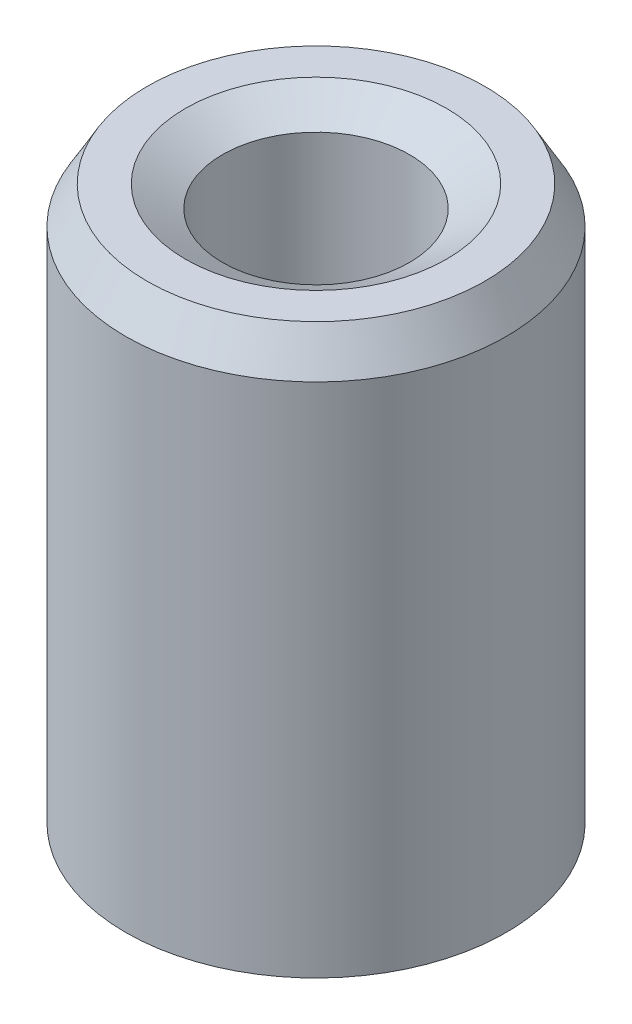
SolidWorks part; units mm, degrees
ref_plane "Front Plane" through (0, 0, 0) normal (0, 0, 1) x (1, 0, 0)
ref_plane "Top Plane" through (0, 0, 0) normal (0, 1, 0) x (1, 0, 0)
ref_plane "Right Plane" through (0, 0, 0) normal (1, 0, 0) x (0, 0, -1)
sketch "Sketch1" plane through (0, 0, 0) normal (0, 1, 0) x (1, 0, 0)
  circle A0 centre (0, 0) radius 5
  dimension "SLEEVE_OD" = 10
extrude "Boss-Extrude1" add sketch "Sketch1" along normal blind 15.102
sketch "Sketch2" plane through (0, 0, 0) normal (0, 1, 0) x (1, 0, 0)
  circle A0 centre (0, 0) radius 2.4577
  dimension "BORE_D" = 4.9153
extrude "Cut-Extrude1" cut sketch "Sketch2" along normal through all
chamfer "Chamfer1" distance 0.9749 angle 30 4 edges at (0, 15.102, 2.4577) (0, 0, 2.4577) (0, 0, 5) (0, 15.102, 5) first distance on face at (0, 15.102, 2.4577) first distance on face at (0, 0, 2.4577) first distance on face at (0, 15.102, 5)
